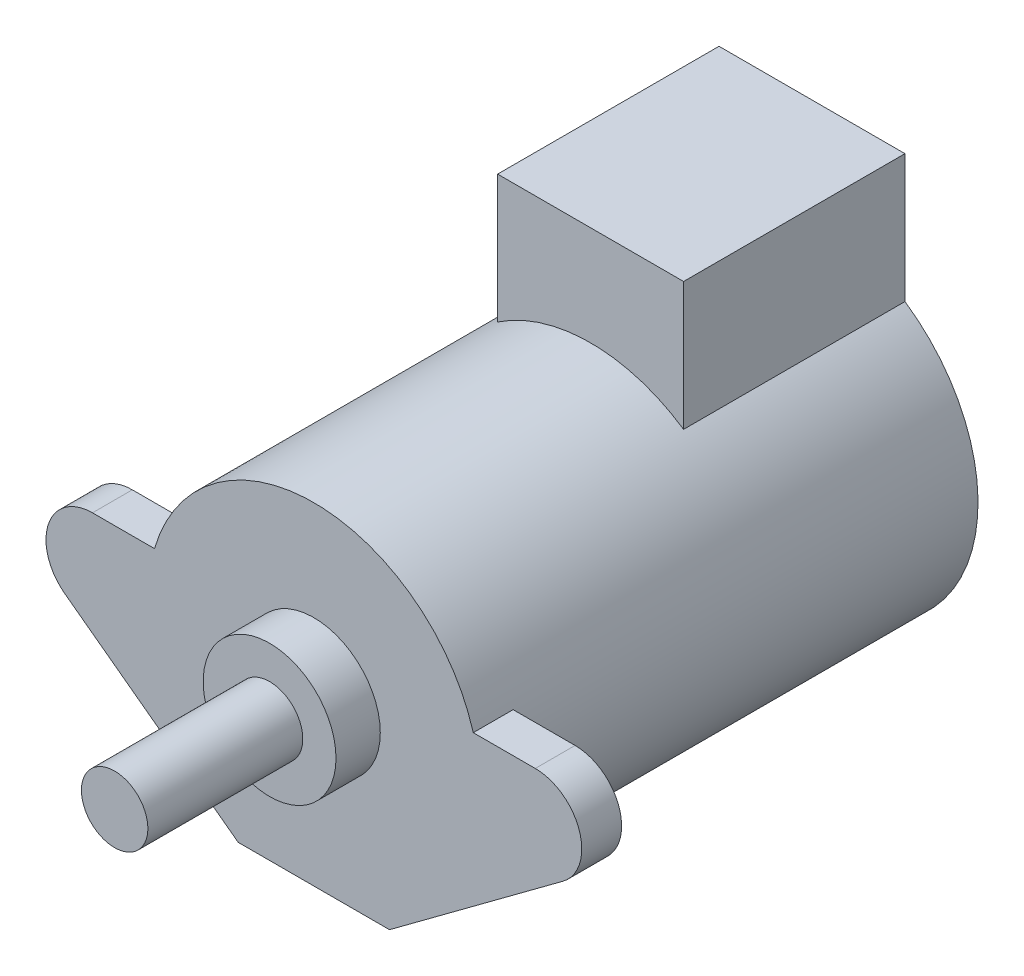
SolidWorks part; units mm, degrees
ref_plane "Front Plane" through (0, 0, 0) normal (0, 0, 1) x (1, 0, 0)
ref_plane "Top Plane" through (0, 0, 0) normal (0, 1, 0) x (1, 0, 0)
ref_plane "Right Plane" through (0, 0, 0) normal (1, 0, 0) x (0, 0, -1)
sketch "Sketch1" plane through (0, 0, 0) normal (0, 0, 1) x (1, 0, 0)
  line L0 (-10, 0) -> (10, 0) construction
  line L1 (-11.2514, -1.6864) -> (-3.417, -7.5)
  line L2 (-3.417, -7.5) -> (3.417, -7.5)
  line L3 (3.417, -7.5) -> (11.2514, -1.6864)
  line L4 (-10, 2.1) -> (-7.2, 2.1)
  line L5 (10, 2.1) -> (7.2, 2.1)
  arc A0 (7.2, 2.1) -> (-7.2, 2.1) centre (0, 0) ccw
  arc A1 (-10, 2.1) -> (-11.2514, -1.6864) centre (-10, 0) ccw
  arc A2 (11.2514, -1.6864) -> (10, 2.1) centre (10, 0) ccw
  point P1 (-3.417, -7.5)
  dimension "D2" = 2.1
  dimension "D3" = 7.5
  dimension "D1" = 20
extrude "Boss-Extrude1" add sketch "Sketch1" along normal blind 22.5
sketch "Sketch2" plane through (0, 0, 22.5) normal (0, 0, 1) x (1, 0, 0)
  circle A0 centre (0, 0) radius 3
  dimension "D1" = 6
extrude "Boss-Extrude2" add sketch "Sketch2" along normal blind 2
sketch "Sketch3" plane through (0, 0, 0) normal (0, 0, -1) x (-1, 0, 0)
  circle A0 centre (0, 0) radius 7.5
  arc A1 (7.2, 2.1) -> (-7.2, 2.1) centre (0, 0) ccw construction
extrude "Cut-Extrude1" cut sketch "Sketch3" against normal offset from surface (20.7 mm away) 1.8 flip side to cut up to face at (3, 0, 22.5)
sketch "Sketch4" plane through (0, 0, 24.5) normal (0, 0, 1) x (1, 0, 0)
  circle A0 centre (0, 0) radius 1.5
  dimension "D1" = 3
extrude "Boss-Extrude3" add sketch "Sketch4" along normal offset from surface (7 mm away) 9 up to face at (3, 0, 22.5) offset beyond the face yes
sketch "Sketch5" plane through (0, 0, 0) normal (0, 0, -1) x (-1, 0, 0)
  line L1 (-4.2, 12) -> (4.2, 12)
  line L2 (-4.2, 12) -> (-4.2, 6.2137)
  line L3 (-4.2, 6.2137) -> (4.2, 6.2137)
  line L4 (4.2, 12) -> (4.2, 6.2137)
  circle A0 centre (0, 0) radius 7.5 construction
  point P6 (-4.5796, 5.9395)
  dimension "D1" = 8.4
  dimension "D2" = 4.5
extrude "Boss-Extrude4" add sketch "Sketch5" against normal blind 10
equation "\"1.82.00mm\"=2"
